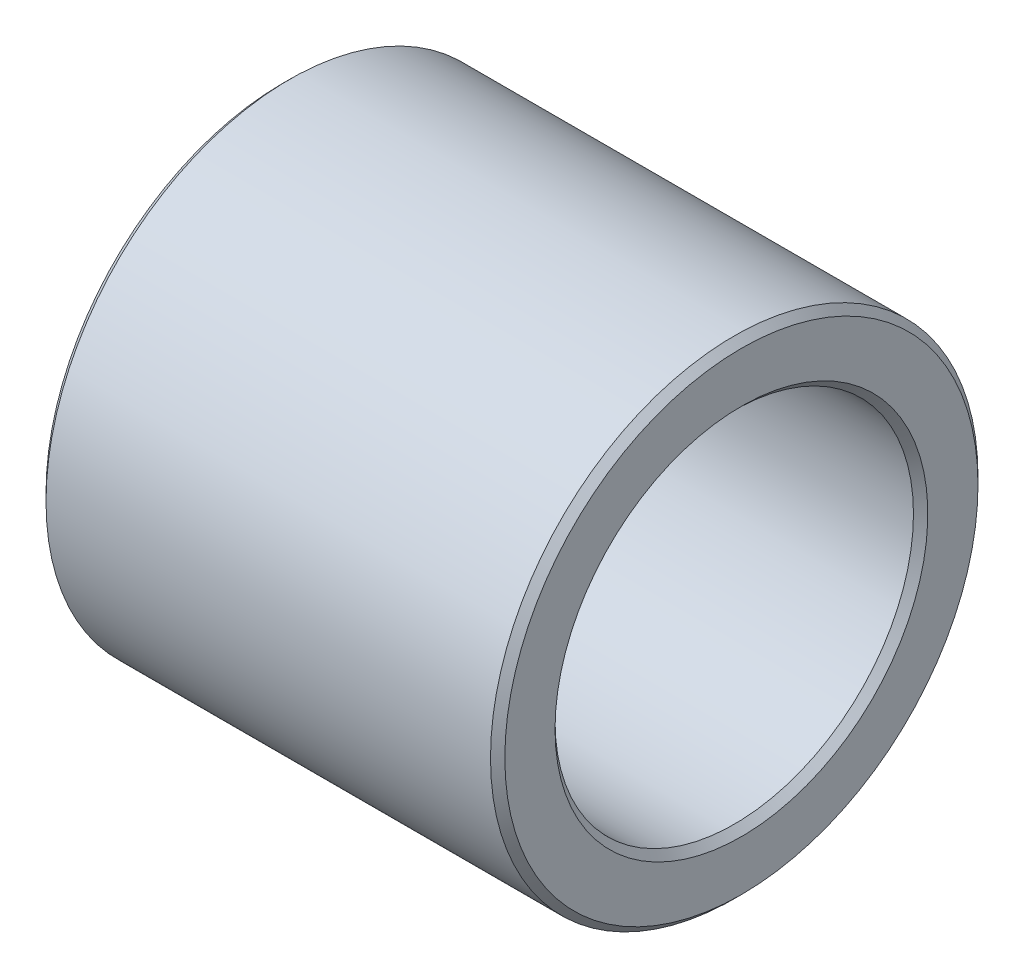
SolidWorks part; units mm, degrees
material "БрАЖ9-4 ГОСТ 18175-78"
ref_plane "Спереди" through (0, 0, 0) normal (0, 0, 1) x (1, 0, 0)
ref_plane "Сверху" through (0, 0, 0) normal (0, 1, 0) x (1, 0, 0)
ref_plane "Справа" through (0, 0, 0) normal (1, 0, 0) x (0, 0, -1)
ref_axis "ОсьX" through (-88.99, 0, 0) along (1, 0, 0)
ref_axis "ОсьZ" through (0, 55, 0) along (0, -1, 0)
ref_axis "ОсьY" through (0, 0, -88.99) along (0, 0, 1)
sketch "Эскиз1" plane through (0, 0, 0) normal (0, 0, 1) x (1, 0, 0)
  line L0 (-15.2284, 0) -> (27.5039, 0) construction
  line L8 (-16, 17) -> (16, 17)
  line L9 (-16, 17) -> (-16, 12.5)
  line L10 (-16, 12.5) -> (16, 12.5)
  line L11 (16, 17) -> (16, 12.5)
  point P7 (0, 12.5)
  dimension "D1" = 25
  dimension "D2" = 34
  dimension "D3" = 32
revolve "Повернуть1" add sketch "Эскиз1" angle 360 mid plane about L0
chamfer "Фаска1" distance 0.5 angle 45 4 edges at (-16, 0, 12.5) (-16, 0, 17) (16, 0, 17) (16, 0, 12.5)
